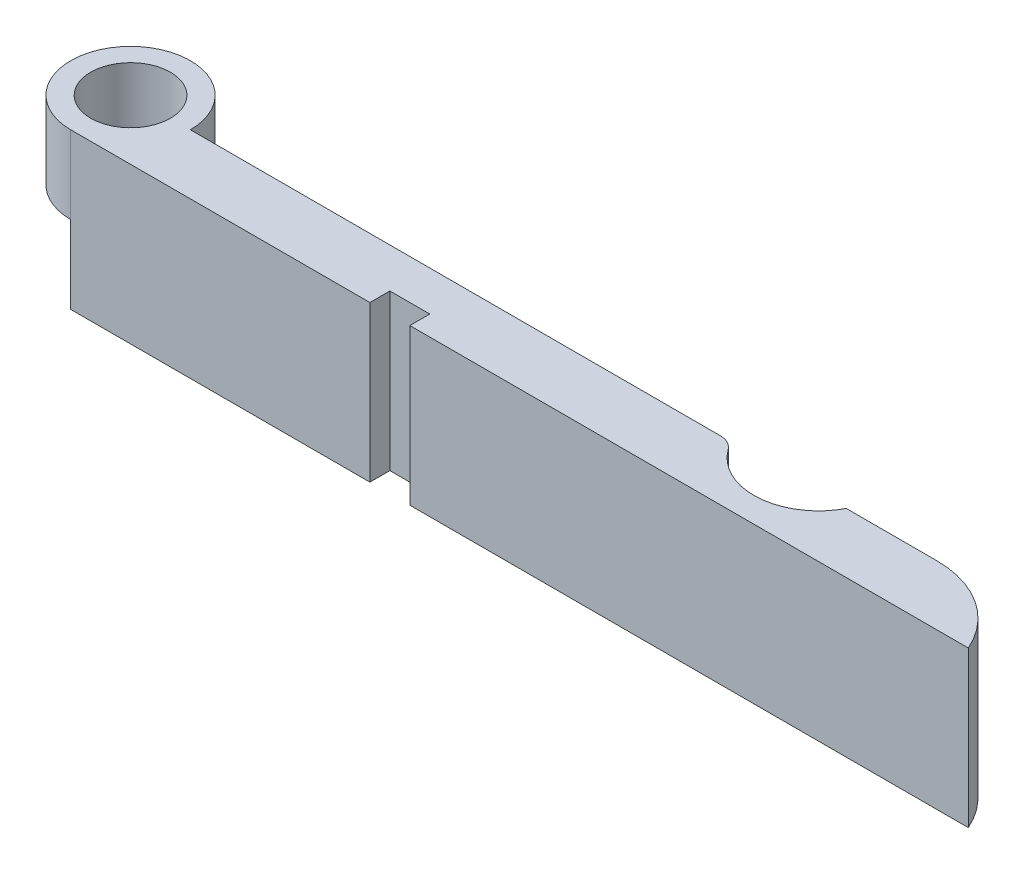
SolidWorks part; units mm, degrees
ref_plane "Alzado" through (0, 0, 0) normal (0, 0, 1) x (1, 0, 0)
ref_plane "Planta" through (0, 0, 0) normal (0, 1, 0) x (1, 0, 0)
ref_plane "Vista lateral" through (0, 0, 0) normal (1, 0, 0) x (0, 0, -1)
sketch "Croquis1" plane through (0, 0, 0) normal (0, 1, 0) x (1, 0, 0)
  line L0 (-14.1349, 0) -> (21.0104, 0) construction
  line L1 (0, 9.8879) -> (0, -9.2182) construction
  circle A0 centre (0, 0) radius 3
  circle A1 centre (0, 0) radius 2
  dimension "D1" = 6
  dimension "D2" = 4
extrude "Saliente-Extruir1" add sketch "Croquis1" along normal blind 3.9
sketch "Croquis3" plane through (0, 0, 0) normal (0, -1, 0) x (1, 0, 0)
  line L0 (0, 4.5432) -> (0, 3) construction
  line L1 (0, 3) -> (45, 3)
  line L2 (45, 3) -> (45, 0)
  line L3 (45, 0) -> (3, 0)
  line L5 (0, 5.0665) -> (0, -5.1763) construction
  circle A0 centre (0, 0) radius 3
  dimension "D1" = 6
  dimension "D2" = 45
  dimension "D3" = 3
extrude "Saliente-Extruir2" add sketch "Croquis3" along normal blind 3.9 and the other way blind 3.9 contours L3 L2 L1 L5 region at (23.6728, 0, 1.5125)
fillet "Redondeo1" radius 5 1 edges at (45, 0, 0)
sketch "Croquis4" plane through (0, -3.9, 0) normal (0, -1, 0) x (1, 0, 0)
  line L0 (0, 3) -> (45, 3) construction
  line L1 (15, 4) -> (17, 4)
  line L2 (15, 4) -> (15, 2)
  line L3 (15, 2) -> (17, 2)
  line L4 (17, 4) -> (17, 2)
  line L5 (15, 4) -> (17, 2) construction
  line L6 (15, 2) -> (17, 4) construction
  line L7 (0, 9.7178) -> (0, -11.9844) construction
  point P0 (16, 3)
  dimension "D1" = 2
  dimension "D2" = 2
  dimension "D3" = 15
extrude "Cortar-Extruir1" cut sketch "Croquis4" against normal through all
sketch "Croquis5" plane through (0, -3.9, 0) normal (0, -1, 0) x (1, 0, 0)
  line L0 (40.4174, 0) -> (3, 0) construction
  circle A0 centre (33, -1.5) radius 3.25
  dimension "D1" = 6.5
  dimension "D2" = 1.5
  dimension "D3" = 33
extrude "Cortar-Extruir2" cut sketch "Croquis5" against normal through all
fillet "Redondeo3" radius 1 1 edges at (30.1169, 0, 0)
